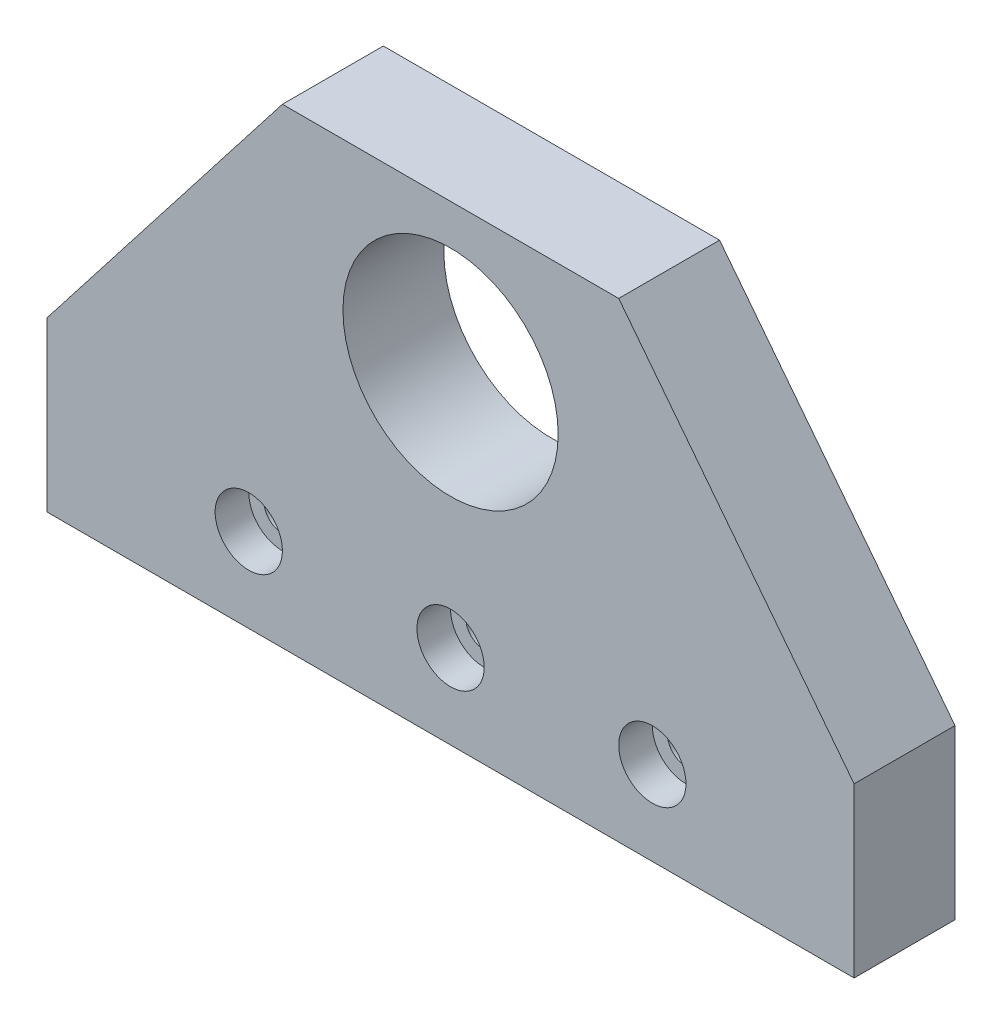
SolidWorks part; units mm, degrees
ref_plane "Front Plane" through (0, 0, 0) normal (0, 0, 1) x (1, 0, 0)
ref_plane "Top Plane" through (0, 0, 0) normal (0, 1, 0) x (1, 0, 0)
ref_plane "Right Plane" through (0, 0, 0) normal (1, 0, 0) x (0, 0, -1)
sketch "Sketch1" plane through (0, 0, 0) normal (0, 0, 1) x (1, 0, 0)
  line L0 (60, 0) -> (-60, 0)
  line L1 (-60, 0) -> (-60, 25)
  line L2 (-60, 25) -> (-25, 70)
  line L3 (-25, 70) -> (25, 70)
  line L4 (0, 0) -> (0, 70) construction
  line L5 (60, 25) -> (25, 70)
  line L6 (60, 0) -> (60, 25)
  dimension "D1" = 120
  dimension "D2" = 25
  dimension "D3" = 50
  dimension "D4" = 70
extrude "Boss-Extrude1" add sketch "Sketch1" along normal blind 15
sketch "Sketch2" plane through (0, 0, 15) normal (0, 0, 1) x (1, 0, 0)
  line L0 (0, 0) -> (0, 70) construction
  line L1 (-60, 0) -> (60, 0) construction
  line L2 (25, 70) -> (-25, 70) construction
  line L3 (-60, 12.5) -> (60, 12.5) construction
  line L4 (-60, 25) -> (-60, 0) construction
  line L5 (60, 0) -> (60, 25) construction
  point P12 (0, 12.5)
  point P13 (-30, 12.5)
  point P14 (30, 12.5)
  point P15 (0, 48)
  dimension "D1" = 30
hole_wizard "CBORE for M5 SHCS1" positions "3DSketch1" profile "Sketch3" counterbore size "M5" standard "ANSI Metric" end condition through all
sketch3d "3DSketch1"
  point P0 (-30, 12.5, 15)
  point P3 (0, 12.5, 15)
  point P6 (30, 12.5, 15)
sketch "Sketch3" plane through (-30, 12.5, 15) normal (1, 0, 0) x (0, -1, 0)
  line L0 (0, 0) -> (0, 15)
  line L1 (0, 15) -> (2.75, 15)
  line L3 (2.75, 15) -> (2.75, 5)
  line L4 (2.75, 5) -> (5, 5)
  line L5 (5, 5) -> (5, 0)
  line L7 (5, 0) -> (0, 0)
  line L11 (0, -6.35) -> (0, 107.95) construction
  dimension "Thru Hole Dia." = 5.5
  dimension "Thru Hole Depth" = 15
  dimension "C'Bore Dia." = 10
  dimension "C'Bore Depth" = 5
sketch "Sketch4" plane through (0, 0, 15) normal (0, 0, 1) x (1, 0, 0)
  circle A0 centre (0, 48) radius 16
  dimension "D1" = 32
extrude "Cut-Extrude1" cut sketch "Sketch4" against normal through all
